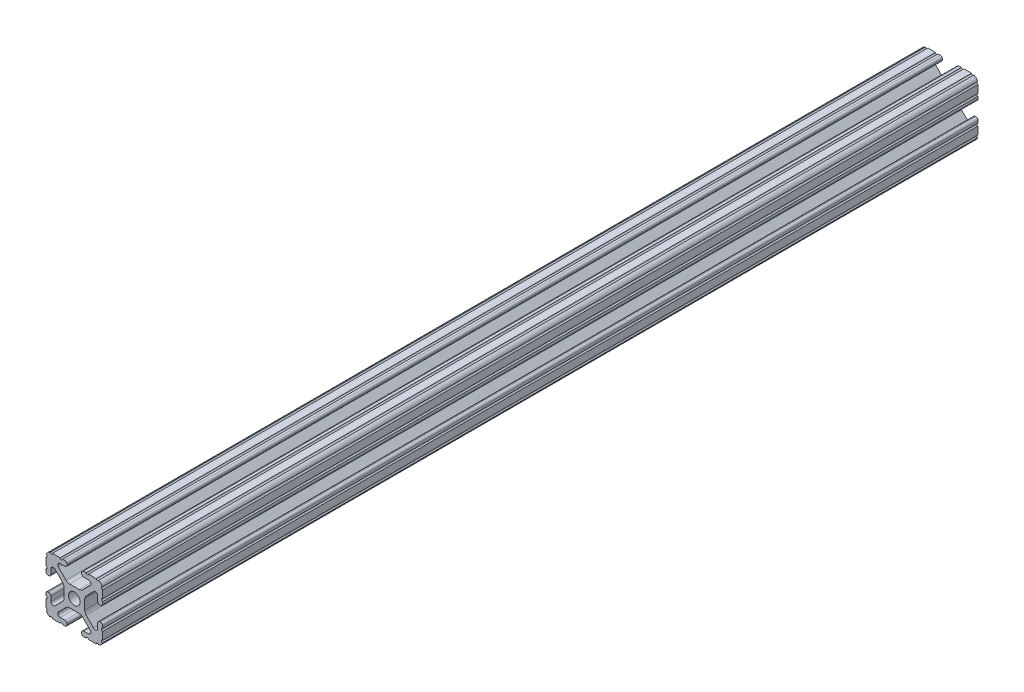
SolidWorks part; units mm, degrees
ref_plane "Front Plane" through (0, 0, 0) normal (0, 0, 1) x (1, 0, 0)
ref_plane "Top Plane" through (0, 0, 0) normal (0, 1, 0) x (1, 0, 0)
ref_plane "Right Plane" through (0, 0, 0) normal (1, 0, 0) x (0, 0, -1)
sketch "Sketch2" plane through (0, 0, 0) normal (0, 0, 1) x (1, 0, 0)
  line L0 (0, 12.7) -> (0, -12.7) construction
  line L1 (-12.7, 0) -> (12.7, 0) construction
  line L2 (3.2512, -12.7) -> (12.7, -12.7)
  line L3 (12.7, -12.7) -> (12.7, -3.2512)
  line L4 (3.2512, -12.7) -> (3.2512, -10.4902)
  line L5 (3.2512, -10.4902) -> (8.9276, -10.4902)
  line L6 (8.9276, -10.4902) -> (3.0856, -4.6482)
  line L7 (0, 0) -> (12.7, -12.7) construction
  line L8 (12.7, -3.2512) -> (10.4902, -3.2512)
  line L9 (10.4902, -3.2512) -> (10.4902, -8.9276)
  line L10 (10.4902, -8.9276) -> (4.6482, -3.0856)
  circle A0 centre (0, 0) radius 2.6035
  arc A1 (6.3485, -10.4902) -> (7.1039, -8.6665) centre (6.3485, -9.4219) ccw construction
  point P8 (0, -4.6482)
  dimension "Center Hole Diameter" = 5.207
  dimension "Rail Height" = 25.4
  dimension "Rail Width" = 25.4
  dimension "T-Slot Width" = 6.5024
  dimension "Slot Inner Width" = 14.8336
  dimension "Thickness" = 2.2098
  dimension "Slot Depth" = 5.842
  dimension "D1" = 2.2098
sketch "Sketch3" plane through (0, 0, 0) normal (1, 0, 0) x (0, 0, -1)
  line L0 (-196.1933, -12.7) -> (196.1933, -12.7) construction
  line L1 (-170.7933, 0) -> (170.7933, 0) construction
  line L3 (196.1933, 0) -> (-196.1933, 0) construction
sketch "Sketch4" plane through (0, 0, 0) normal (0, 0, 1) x (1, 0, 0)
  line L0 (4.1904, -12.7) -> (10.1173, -12.7)
  line L1 (3.2512, -12.7) -> (12.7, -12.7) construction
  line L2 (3.2512, -12.7) -> (3.2512, -10.4902) construction
  line L3 (3.2512, -10.4902) -> (8.9276, -10.4902) construction
  line L4 (3.2512, -11.4294) -> (3.2512, -11.7608)
  line L5 (4.1904, -10.4902) -> (6.3485, -10.4902)
  line L6 (0, -4.6482) -> (2.164, -4.6482)
  line L7 (8.9276, -10.4902) -> (3.0856, -4.6482) construction
  line L8 (3.7373, -5.2999) -> (7.1039, -8.6665)
  line L9 (12.7, -12.7) -> (12.7, -3.2512) construction
  line L10 (10.4902, -8.9276) -> (4.6482, -3.0856) construction
  line L11 (10.4902, -3.2512) -> (10.4902, -8.9276) construction
  line L12 (10.4902, -6.3485) -> (10.4902, -4.1904)
  line L13 (12.7, -3.2512) -> (10.4902, -3.2512) construction
  line L14 (11.4294, -3.2512) -> (11.7608, -3.2512)
  line L15 (12.7, -4.1904) -> (12.7, -10.1173)
  line L16 (8.6665, -7.1039) -> (5.2999, -3.7373)
  line L17 (4.6482, 0) -> (4.6482, -2.164)
  line L18 (-12.7, 0) -> (12.7, 0) construction
  line L19 (0, -4.6482) -> (0, -2.6035)
  line L20 (0, 12.7) -> (0, -12.7) construction
  line L21 (4.6482, 0) -> (2.6035, 0)
  arc A0 (3.2512, -11.7608) -> (4.1904, -12.7) centre (4.1904, -11.7608) ccw
  arc A2 (3.2512, -11.4294) -> (4.1904, -10.4902) centre (4.1904, -11.4294) cw
  arc A3 (6.3485, -10.4902) -> (7.1039, -8.6665) centre (6.3485, -9.4219) ccw
  arc A4 (2.164, -4.6482) -> (3.7373, -5.2999) centre (2.164, -6.8732) cw
  arc A5 (10.1173, -12.7) -> (12.7, -10.1173) centre (10.1173, -10.1173) ccw
  arc A6 (8.6665, -7.1039) -> (10.4902, -6.3485) centre (9.4219, -6.3485) ccw
  arc A7 (10.4902, -4.1904) -> (11.4294, -3.2512) centre (11.4294, -4.1904) cw
  arc A8 (11.7608, -3.2512) -> (12.7, -4.1904) centre (11.7608, -4.1904) cw
  arc A9 (5.2999, -3.7373) -> (4.6482, -2.164) centre (6.8732, -2.164) cw
  circle A10 centre (0, 0) radius 2.6035 construction
  arc A11 (0, -2.6035) -> (2.6035, 0) centre (0, 0) ccw
  dimension "D1" = 2.5827
  dimension "D2" = 2.225
  dimension "D3" = 0.9392
extrude "Boss-Extrude1" add sketch "Sketch4" along normal up to vertex (196.1933 mm away) from vertex up to point (0, -12.7, 196.1933) starting at point (0, -12.7, -196.1933)
sketch "Sketch5" plane through (0, 0, 0) normal (0, 0, 1) x (1, 0, 0)
  line L0 (3.2512, -12.7) -> (12.7, -12.7) construction
  line L1 (4.1904, -10.4902) -> (6.3485, -10.4902) construction
  line L3 (0, 0) -> (12.7, -12.7) construction
  line L4 (6.3485, -10.4902) -> (6.3485, -12.7) construction
  line L5 (8.9276, -10.4902) -> (3.0856, -4.6482) construction
  circle A0 centre (10.3562, -12.7) radius 0.5524
  circle A1 centre (5.796, -12.7) radius 0.5524
  circle A2 centre (12.7, -10.3562) radius 0.5524
  circle A3 centre (12.7, -5.796) radius 0.5524
  point P10 (5.2694, -10.4902)
  point P12 (9.4219, -6.3485)
  dimension "D1" = 1.1049
extrude "Cut-Extrude1" cut sketch "Sketch5" against normal through all both and the other way through all
mirror "Mirror1" about plane through (0, 0, 0) normal (1, 0, 0) of bodies 137 134
mirror "Mirror2" about plane through (0, 0, 0) normal (0, 1, 0) of bodies 135
equation "\"D1@Sketch2\"=\"Thickness@Sketch2\""
equation "\"D2@Sketch4\"=\"Slot Inner Width@Sketch2\"*0.15"
equation "\"D1@Sketch4\"=\"D3@Sketch4\"*2.75"
equation "\"D3@Sketch4\"=\"Thickness@Sketch2\"*0.425"
equation "\"D1@Sketch5\"=\"Thickness@Sketch2\"*0.5"
equation "\"D1@Boss-Extrude1\"=\"Length@Sketch3\""
